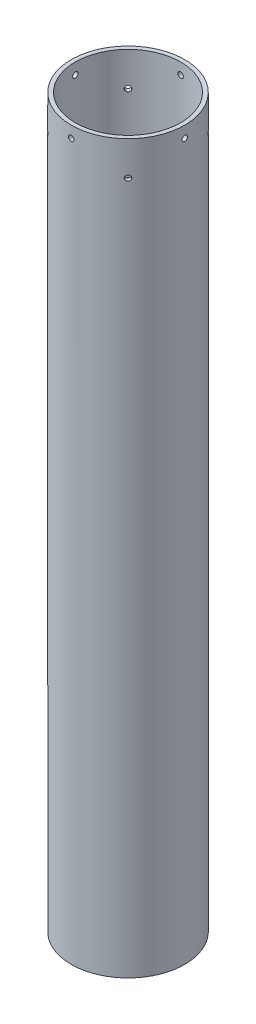
SolidWorks part; units mm, degrees
material "ПВХ 0.007 Смягченный"
ref_plane "Спереди" through (0, 0, 0) normal (0, 0, 1) x (1, 0, 0)
ref_plane "Сверху" through (0, 0, 0) normal (0, 1, 0) x (1, 0, 0)
ref_plane "Справа" through (0, 0, 0) normal (1, 0, 0) x (0, 0, -1)
sketch "Эскиз1" plane through (0, 0, 0) normal (0, 1, 0) x (1, 0, 0)
  circle A0 centre (0, 0) radius 25
  circle A1 centre (0, 0) radius 23.2
  dimension "ExDBody" = 50
  dimension "InDBody" = 46.4
extrude "Бобышка-Вытянуть1" add sketch "Эскиз1" along normal blind 320
sketch "Эскиз2" plane through (0, 0, 0) normal (1, 0, 0) x (0, 0, -1)
  line L0 (23.2, 320) -> (-23.2, 320) construction
  circle A0 centre (0, 315) radius 1.2
  dimension "D1" = 5
  dimension "D2" = 2.4
extrude "Вырез-Вытянуть1" cut sketch "Эскиз2" against normal through all
pattern_circular "Круговой массив1" count 4 over 360 about axis through (0, 320, 0) along (0, -1, 0) of "Вырез-Вытянуть1"
ref_plane "Плоскость1" through (0, 0, 0) normal (-0.7071, 0, 0.7071) x (0, -1, 0)
sketch "Эскиз3" plane through (0, 0, 0) normal (-0.7071, 0, 0.7071) x (0, -1, 0)
  line L0 (-320, 0) -> (0, 0) construction
  line L1 (-320, 25) -> (-320, -25) construction
  circle A0 centre (-305, 0) radius 1.2
  dimension "D1" = 2.4
  dimension "D2" = 15
extrude "Вырез-Вытянуть2" cut sketch "Эскиз3" against normal through all
pattern_circular "Круговой массив2" count 4 over 360 about axis through (0, 320, 0) along (0, -1, 0) of "Вырез-Вытянуть2"
